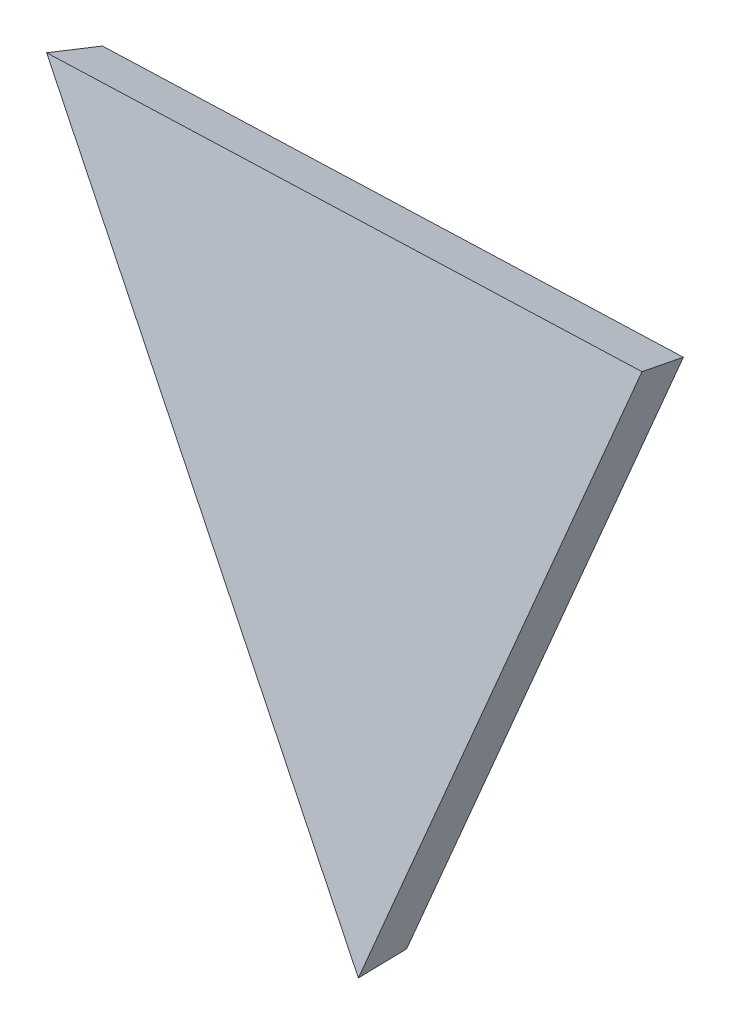
SolidWorks part; units mm, degrees
ref_plane "Front Plane" through (0, 0, 0) normal (0, 0, 1) x (1, 0, 0)
ref_plane "Top Plane" through (0, 0, 0) normal (0, 1, 0) x (1, 0, 0)
ref_plane "Right Plane" through (0, 0, 0) normal (1, 0, 0) x (0, 0, -1)
ref_plane "Plane2" through (5.8073, -651.6748, -3268.6876) normal (-0.0017, 0.1955, 0.9807) x (0.9851, 0.1692, -0.032)
sketch "Sketch1" plane through (5.4738, -457.938, -3307.3133) normal (-0.0017, 0.1955, 0.9807) x (-0.9856, 0.1652, -0.0347)
  line L0 (1127.4106, 6899.993) -> (1231.7883, 7721.0989)
  line L1 (1231.7883, 7721.0989) -> (1938.3645, 7065.7137)
  line L2 (1938.3645, 7065.7137) -> (1127.4106, 6899.993)
extrude "Boss-Extrude1" add sketch "Sketch1" against normal blind 70
chamfer "Chamfer1" distance 70 angle 3.425 1 edges at (-2804.8126, -7356.8203, -2008.2611) first distance on face at (-2804.8735, -7349.9771, -1973.9367)
chamfer "Chamfer2" distance 70 angle 5.725 2 edges at (-2681.4923, -6968.4868, -2085.4636) (-2390.4161, -7341.2953, -2010.6201) first distance on face at (-2682.8408, -6961.6844, -2051.1333) first distance on face at (-2390.8529, -7335.6605, -1976.0554)
equation "\"D1@Boss-Extrude1\" = \"wall_thick@4Vcorrection.Assembly\""
equation "\"E\"= \"E@4Vcorrection.Assembly\""
equation "\"Thick\"= \"wall_thick@4Vcorrection.Assembly\""
equation "\"D1@Chamfer1\"=\"Thick\""
equation "\"D2@Chamfer1\"=\"E\""
equation "\"F\"= \"F@4Vcorrection.Assembly\""
equation "\"D1@Chamfer2\"=\"Thick\""
equation "\"D2@Chamfer2\"=\"F\""
